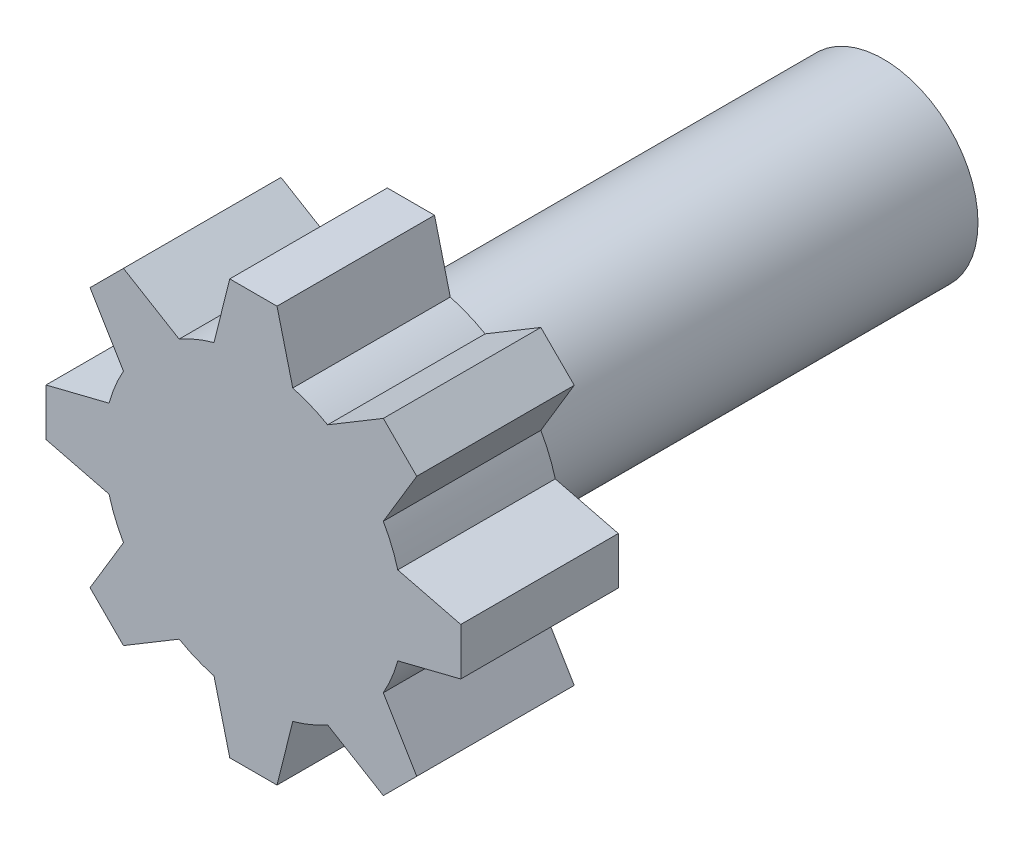
SolidWorks part; units mm, degrees
ref_plane "Front Plane" through (0, 0, 0) normal (0, 0, 1) x (1, 0, 0)
ref_plane "Top Plane" through (0, 0, 0) normal (0, 1, 0) x (1, 0, 0)
ref_plane "Right Plane" through (0, 0, 0) normal (1, 0, 0) x (0, 0, -1)
sketch "Esquisse1" plane through (0, 0, 0) normal (0, 0, 1) x (1, 0, 0)
  circle A0 centre (0, 0) radius 4.75
  point P9 (0, 0)
  point P10 (1.6023, 3.665)
  dimension "D1" = 9.5
extrude "Main Extrusion" add sketch "Esquisse1" along normal blind 5
sketch "Esquisse2" plane through (0, 0, 5) normal (0, 0, 1) x (1, 0, 0)
  line L0 (-1.25, 4.5826) -> (1.25, 4.5826)
  line L1 (1.25, 4.5826) -> (0.75, 6.5826)
  line L2 (0.75, 6.5826) -> (-0.75, 6.5826)
  line L3 (-0.75, 6.5826) -> (-1.25, 4.5826)
  circle A0 centre (0, 0) radius 4.75 construction
  point P3 (0, 4.5826)
  point P6 (0, 0)
  dimension "D1" = 2.5
  dimension "D2" = 1.5
  dimension "D3" = 2
extrude "Gear Element" add sketch "Esquisse2" against normal up to surface (5 mm away) up to face at (4.75, 0, 0)
ref_axis "Axe1" through (0, 0, -0.25) along (0, 0, 1)
pattern_circular "Répétition circulaire1" count 8 every 45 about axis through (0, 0, -0.25) along (0, 0, 1) of "Gear Element"
sketch "Esquisse3" plane through (0, 0, 0) normal (0, 0, -1) x (-1, 0, 0)
  circle A0 centre (0, 0) radius 3
  point P2 (0, 0)
  dimension "D1" = 6
extrude "Main Axe" add sketch "Esquisse3" along normal blind 15
sketch "Esquisse4" plane through (0, 0, -15) normal (0, 0, -1) x (-1, 0, 0)
  line L1 (-2, 0.5) -> (2, 0.5)
  line L2 (-2, 0.5) -> (-2, -0.5)
  line L3 (-2, -0.5) -> (2, -0.5)
  line L4 (2, 0.5) -> (2, -0.5)
  point P4 (-2, 0)
  point P6 (0, 0)
  point P7 (0, 0.5)
  dimension "D1" = 1
  dimension "D2" = 4
extrude "Axe Trait" cut sketch "Esquisse4" against normal blind 3
